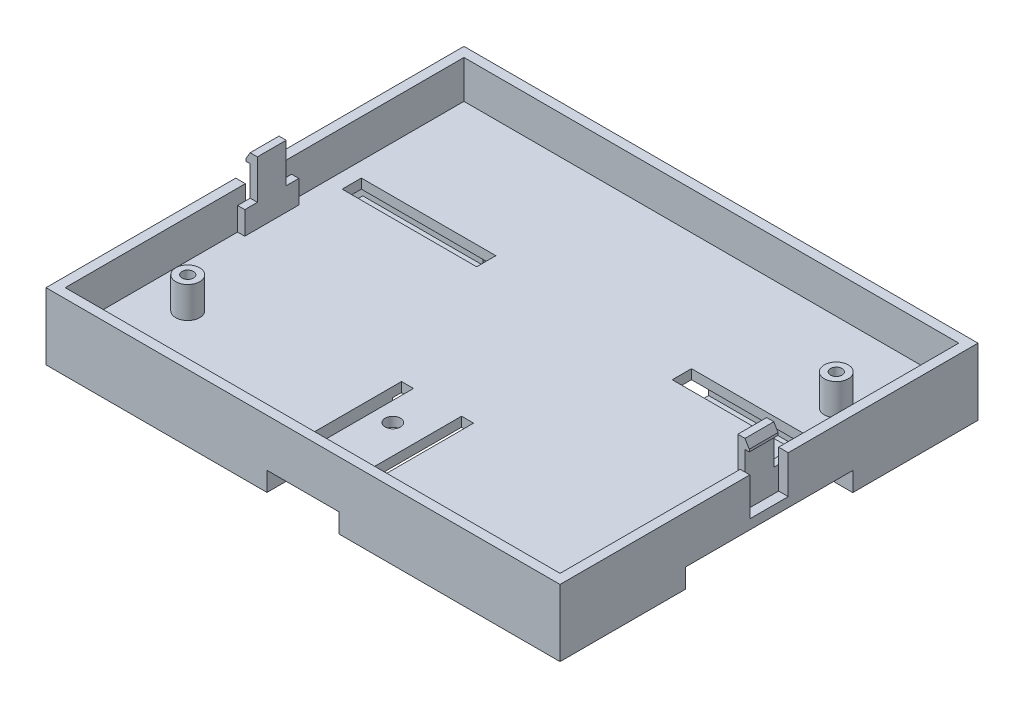
SolidWorks part; units mm, degrees
ref_plane "Front Plane" through (0, 0, 0) normal (0, 0, 1) x (1, 0, 0)
ref_plane "Top Plane" through (0, 0, 0) normal (0, 1, 0) x (1, 0, 0)
ref_plane "Right Plane" through (0, 0, 0) normal (1, 0, 0) x (0, 0, -1)
sketch "Sketch1" plane through (0, 0, 0) normal (0, 1, 0) x (1, 0, 0)
  line L1 (-53.5, 43.5) -> (53.5, 43.5)
  line L2 (-53.5, 43.5) -> (-53.5, -43.5)
  line L3 (-53.5, -43.5) -> (53.5, -43.5)
  line L4 (53.5, 43.5) -> (53.5, -43.5)
  line L5 (-53.5, 43.5) -> (53.5, -43.5) construction
  line L6 (-53.5, -43.5) -> (53.5, 43.5) construction
  point P0 (0, 0)
  dimension "D1" = 107
  dimension "D2" = 87
extrude "Boss-Extrude1" add sketch "Sketch1" along normal blind 13.92
sketch "Sketch2" plane through (0, 13.92, 0) normal (0, 1, 0) x (1, 0, 0)
  line L0 (53.5, -43.5) -> (53.5, 43.5) construction
  line L1 (-51.5, 41.5) -> (51.5, 41.5)
  line L2 (-51.5, 41.5) -> (-51.5, -41.5)
  line L3 (-51.5, -41.5) -> (51.5, -41.5)
  line L4 (51.5, 41.5) -> (51.5, -41.5)
  line L5 (-51.5, 41.5) -> (51.5, -41.5) construction
  line L6 (-51.5, -41.5) -> (51.5, 41.5) construction
  line L7 (53.5, 43.5) -> (-53.5, 43.5) construction
  point P0 (0, 0)
  dimension "D1" = 2
  dimension "D2" = 2
extrude "Cut-Extrude1" cut sketch "Sketch2" against normal blind 7.92
sketch "Sketch3" plane through (0, 6, 0) normal (0, 1, 0) x (1, 0, 0)
  line L0 (0, 0) -> (-42.5, 0)
  line L1 (-42.5, 0) -> (-42.5, -25)
  line L2 (0, 0) -> (42.5, 0)
  line L3 (42.5, 0) -> (42.5, 25)
  circle A0 centre (-42.5, -25) radius 1.2
  circle A1 centre (-42.5, -25) radius 2.5
  circle A2 centre (42.5, 25) radius 1.2
  circle A3 centre (42.5, 25) radius 2.5
  dimension "D1" = 2.4
  dimension "D2" = 5
  dimension "D3" = 2.4
  dimension "D4" = 5
  dimension "D5" = 42.5
  dimension "D6" = 42.5
  dimension "D7" = 25
  dimension "D8" = 25
extrude "Boss-Extrude2" add sketch "Sketch3" along normal blind 6.5 contours A1 | A3
sketch "Sketch4" plane through (0, 6, 0) normal (0, 1, 0) x (1, 0, 0)
  circle A0 centre (-42.5, -25) radius 1.2
  circle A1 centre (42.5, 25) radius 1.2
  dimension "D1" = 2.4
  dimension "D2" = 2.4
extrude "Cut-Extrude2" cut sketch "Sketch4" against normal blind 4 and the other way through all
sketch "Sketch5" plane through (0, 6, 0) normal (0, 1, 0) x (1, 0, 0)
  line L0 (-51.5, 41.5) -> (-51.5, -41.5) construction
  line L1 (-48.36, 17) -> (-20.36, 17)
  line L2 (-48.36, 17) -> (-48.36, 13)
  line L3 (-48.36, 13) -> (-20.36, 13)
  line L4 (-20.36, 17) -> (-20.36, 13)
  line L5 (0, 0) -> (0, 41.5) construction
  line L7 (51.5, 41.5) -> (-51.5, 41.5) construction
  line L9 (0, 0) -> (0, -41.5) construction
  line L10 (-51.5, -41.5) -> (51.5, -41.5) construction
  line L11 (0, 0) -> (-51.5, 0) construction
  line L12 (48.36, 13) -> (20.36, 13)
  line L13 (20.36, 17) -> (20.36, 13)
  line L14 (48.36, 17) -> (20.36, 17)
  line L15 (48.36, 17) -> (48.36, 13)
  dimension "D1" = 3.14
  dimension "D2" = 28
  dimension "D3" = 4
  dimension "D4" = 13
extrude "Cut-Extrude3" cut sketch "Sketch5" against normal through all
sketch "Sketch6" plane through (0, 6, 0) normal (0, 1, 0) x (1, 0, 0)
  line L0 (0, 0) -> (0, -41.5) construction
  line L1 (-51.5, -41.5) -> (51.5, -41.5) construction
  line L2 (5, -15.5) -> (5, -39.5)
  line L3 (-7.5, -15.5) -> (-5, -15.5)
  line L4 (-7.5, -15.5) -> (-7.5, -39.5)
  line L5 (-7.5, -39.5) -> (-5, -39.5)
  line L6 (-5, -15.5) -> (-5, -39.5)
  line L7 (7.5, -39.5) -> (5, -39.5)
  line L8 (7.5, -15.5) -> (7.5, -39.5)
  line L9 (7.5, -15.5) -> (5, -15.5)
  point P9 (0, -20.75)
  dimension "D1" = 24
  dimension "D2" = 2.5
  dimension "D3" = 5
  dimension "D4" = 2
extrude "Cut-Extrude4" cut sketch "Sketch6" against normal through all
sketch "Sketch7" plane through (0, 6, 0) normal (0, 1, 0) x (1, 0, 0)
  line L0 (0, 0) -> (0, -41.5) construction
  line L1 (-51.5, -41.5) -> (51.5, -41.5) construction
  circle A0 centre (-1, -23.8) radius 1.6
  dimension "D1" = 3.2
  dimension "D2" = 1
  dimension "D3" = 23.8
extrude "Cut-Extrude6" cut sketch "Sketch7" against normal through all
sketch "Sketch8" plane through (-53.5, 0, 0) normal (-1, 0, 0) x (0, 0, 1)
  line L0 (0, 0) -> (0, 13.92) construction
  line L1 (-43.5, 13.92) -> (43.5, 13.92) construction
  line L3 (-4, 13.92) -> (4, 13.92)
  line L4 (-4, 13.92) -> (-4, 6)
  line L5 (-4, 6) -> (4, 6)
  line L6 (4, 13.92) -> (4, 6)
  dimension "D1" = 8
  dimension "D2" = 7.92
extrude "Cut-Extrude9" cut sketch "Sketch8" against normal blind 4
sketch "Sketch9" plane through (0, 6, 0) normal (0, 1, 0) x (1, 0, 0)
  line L0 (-51.5, 5.625) -> (-51.5, -5.625)
  line L1 (-51.5, 41.5) -> (-51.5, 4) construction
  line L2 (-51.5, -4) -> (-51.5, -41.5) construction
  line L3 (-51.5, -5.625) -> (-50, -5.625)
  line L4 (-50, -5.625) -> (-50, 5.625)
  line L5 (-50, 5.625) -> (-51.5, 5.625)
  line L6 (-53.5, 0) -> (0, 0) construction
  line L7 (-53.5, 4) -> (-53.5, -4) construction
  dimension "D1" = 11.25
  dimension "D2" = 1.5
extrude "Boss-Extrude4" add sketch "Sketch9" along normal blind 4.8
sketch "Sketch10" plane through (0, 10.8, 0) normal (0, 1, 0) x (1, 0, 0)
  line L0 (-51.5, 0) -> (-50, 0) construction
  line L1 (-51.5, 4) -> (-51.5, -4) construction
  line L2 (-50, -5.625) -> (-50, 5.625) construction
  line L3 (-51.5, 4) -> (-51.5, -4) construction
  line L4 (-51.5, 3) -> (-50, 3)
  line L5 (-51.5, 3) -> (-51.5, -3)
  line L6 (-51.5, -3) -> (-50, -3)
  line L7 (-50, 3) -> (-50, -3)
  dimension "D1" = 6
extrude "Boss-Extrude5" add sketch "Sketch10" along normal blind 8.2
sketch "Sketch11" plane through (0, 0, 3) normal (0, 0, 1) x (1, 0, 0)
  line L0 (-51.5, 19) -> (-52.4, 17.5)
  line L1 (-52.4, 17.5) -> (-52.4, 17)
  line L2 (-52.4, 17) -> (-51.5, 17)
  line L3 (-51.5, 19) -> (-51.5, 10.8) construction
  line L4 (-51.5, 17) -> (-51.5, 19)
  dimension "D1" = 0.9
  dimension "D2" = 0.5
  dimension "D3" = 2
extrude "Boss-Extrude6" add sketch "Sketch11" against normal blind 6
mirror "Mirror2" about plane through (0, 0, 0) normal (1, 0, 0) of "Boss-Extrude6", "Boss-Extrude5", "Boss-Extrude4", "Cut-Extrude9"
sketch "Sketch12" plane through (0, 0, 0) normal (0, -1, 0) x (1, 0, 0)
  line L0 (53.5, 43.5) -> (53.5, -43.5) construction
  line L1 (-51.5, 41.5) -> (51.5, 41.5)
  line L2 (-51.5, 41.5) -> (-51.5, -41.5)
  line L3 (-51.5, -41.5) -> (51.5, -41.5)
  line L4 (51.5, 41.5) -> (51.5, -41.5)
  line L5 (-51.5, 41.5) -> (51.5, -41.5) construction
  line L6 (-51.5, -41.5) -> (51.5, 41.5) construction
  line L7 (-53.5, 43.5) -> (53.5, 43.5) construction
  point P0 (0, 0)
  dimension "D1" = 2
  dimension "D2" = 2
extrude "Cut-Extrude10" cut sketch "Sketch12" against normal blind 4
sketch "Sketch13" plane through (-53.5, 0, 0) normal (-1, 0, 0) x (0, 0, 1)
  line L0 (0, 0) -> (0, 19) construction
  line L1 (-3, 19) -> (3, 19) construction
  line L2 (-43.5, 0) -> (43.5, 0) construction
  line L3 (-17.435, 4) -> (17.435, 4)
  line L4 (-17.435, 4) -> (-17.435, 0)
  line L5 (-17.435, 0) -> (17.435, 0)
  line L6 (17.435, 4) -> (17.435, 0)
  dimension "D1" = 4
  dimension "D2" = 34.87
extrude "Cut-Extrude11" cut sketch "Sketch13" against normal through all
sketch "Sketch14" plane through (0, 4, 0) normal (0, -1, 0) x (-1, 0, 0)
  line L9 (51.5, 17.435) -> (23.5, 17.435)
  line L10 (23.5, 17.435) -> (23.5, 19.935)
  line L11 (23.5, 19.935) -> (51.5, 19.935)
  line L12 (51.5, 17.435) -> (51.5, 41.5) construction
  line L13 (51.5, 19.935) -> (51.5, 17.435)
  line L15 (53.5, 43.5) -> (53.5, 17.435) construction
  point P2 (0, 0)
  dimension "D1" = 2.5
  dimension "D2" = 30
extrude "Boss-Extrude9" add sketch "Sketch14" along normal blind 4
sketch "Sketch15" plane through (-23.5, 0, 0) normal (1, 0, 0) x (0, 0, -1)
  line L0 (17.435, 0) -> (14.935, 0)
  line L1 (14.935, 0) -> (14.935, 1)
  line L2 (14.935, 1) -> (16.435, 2.5)
  line L3 (16.435, 2.5) -> (17.435, 2.5)
  line L4 (17.435, 0) -> (17.435, 4) construction
  line L5 (17.435, 2.5) -> (17.435, 0)
  dimension "D1" = 2.5
  dimension "D2" = 2.5
  dimension "D3" = 1.5
  dimension "D4" = 45
extrude "Boss-Extrude10" add sketch "Sketch15" against normal blind 25
mirror "Mirror8" about plane through (0, 0, 0) normal (1, 0, 0) of "Boss-Extrude10", "Boss-Extrude9", "Cut-Extrude11"
extrude "Boss-Extrude11" add sketch "Sketch15<2>" against normal blind 25
sketch "Sketch15<2>" plane through (-23.5, 0, 0) normal (1, 0, 0) x (0, 0, -1) same geometry as "Sketch15"
sketch "Sketch16" plane through (0, 0, 43.5) normal (0, 0, 1) x (1, 0, 0)
  line L0 (0, 0) -> (0, 13.92) construction
  line L1 (-53.5, 13.92) -> (53.5, 13.92) construction
  line L2 (-53.5, 0) -> (53.5, 0) construction
  line L3 (-7.5, 4) -> (7.5, 4)
  line L4 (-7.5, 4) -> (-7.5, 0)
  line L5 (-7.5, 0) -> (7.5, 0)
  line L6 (7.5, 4) -> (7.5, 0)
  dimension "D1" = 15
  dimension "D2" = 4
extrude "Cut-Extrude12" cut sketch "Sketch16" against normal through all
sketch "Sketch18" plane through (0, 4, 0) normal (0, -1, 0) x (-1, 0, 0)
  line L0 (7.5, -41.5) -> (7.5, -17.37)
  line L1 (7.5, -15.5) -> (7.5, -39.5) construction
  line L2 (7.5, -17.37) -> (39.5, -17.37)
  line L3 (39.5, -17.37) -> (43.5, -19.0173)
  line L4 (43.5, -19.0173) -> (42.75, -20.8385)
  line L5 (42.75, -20.8385) -> (39.5, -19.5)
  line L6 (39.5, -19.5) -> (10.5, -19.5)
  line L7 (10.5, -19.5) -> (10.5, -41.5)
  line L8 (7.5, -41.5) -> (51.5, -41.5) construction
  line L9 (10.5, -41.5) -> (7.5, -41.5)
  point P13 (38.6986, -19.0942)
  point P14 (0, 0)
  point P16 (38.6407, -19.5)
  dimension "D1" = 36
  dimension "D2" = 26.13
  dimension "D3" = 22
  dimension "D4" = 33
  dimension "D5" = 4
  dimension "D6" = 3.25
extrude "Boss-Extrude12" add sketch "Sketch18" along normal blind 4
mirror "Mirror9" about plane through (0, 0, 0) normal (1, 0, 0) of "Cut-Extrude12", "Boss-Extrude12"
